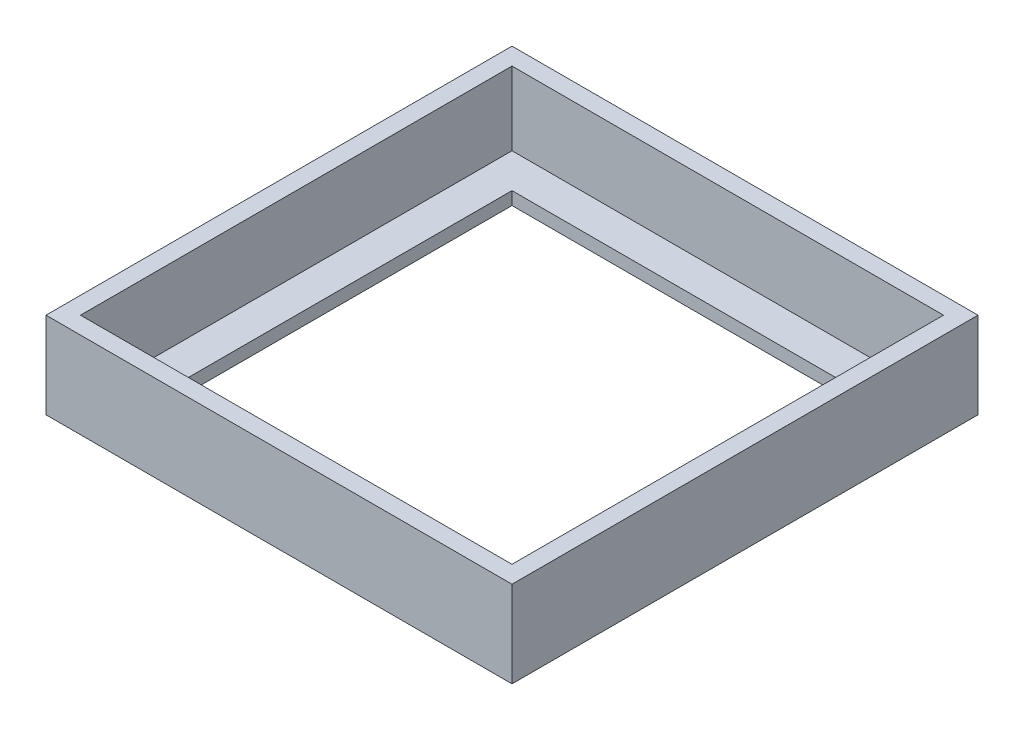
SolidWorks part; units mm, degrees
note: The reader was unsure of these and kept them because the rebuilt part matched: shared geometry of "Sketch1<19>".
ref_plane "Front Plane" through (0, 0, 0) normal (0, 0, 1) x (1, 0, 0)
ref_plane "Top Plane" through (0, 0, 0) normal (0, 1, 0) x (1, 0, 0)
ref_plane "Right Plane" through (0, 0, 0) normal (1, 0, 0) x (0, 0, -1)
sketch "Sketch1" plane through (0, 0, 0) normal (0, 1, 0) x (1, 0, 0)
  line L1 (-46, 33) -> (8, 33)
  line L2 (-40, 27) -> (2, 27)
  line L3 (-40, 27) -> (-40, -15)
  line L4 (-40, -15) -> (2, -15)
  line L5 (2, 27) -> (2, -15)
  line L6 (-46, 33) -> (-46, -21)
  line L7 (-46, -21) -> (8, -21)
  line L8 (8, 33) -> (8, -21)
  line L82 (-44, 31) -> (6, 31)
  line L83 (-44, 31) -> (-44, -19)
  line L84 (-44, -19) -> (6, -19)
  line L85 (6, 31) -> (6, -19)
extrude "Boss-Extrude8" add sketch "Sketch1" along normal blind 1.5 contours L85 L82 L83 L84 L2 L5 L4 L3 | L5 L2 L3 L4
extrude "Boss-Extrude9" add sketch "Sketch1<19>" along normal blind 10 contours L8 L1 L6 L7 L82 L85 L84 L83
sketch "Sketch1<19>" plane through (0, 0, 0) normal (0, 1, 0) x (1, 0, 0) same geometry as "Sketch1"
